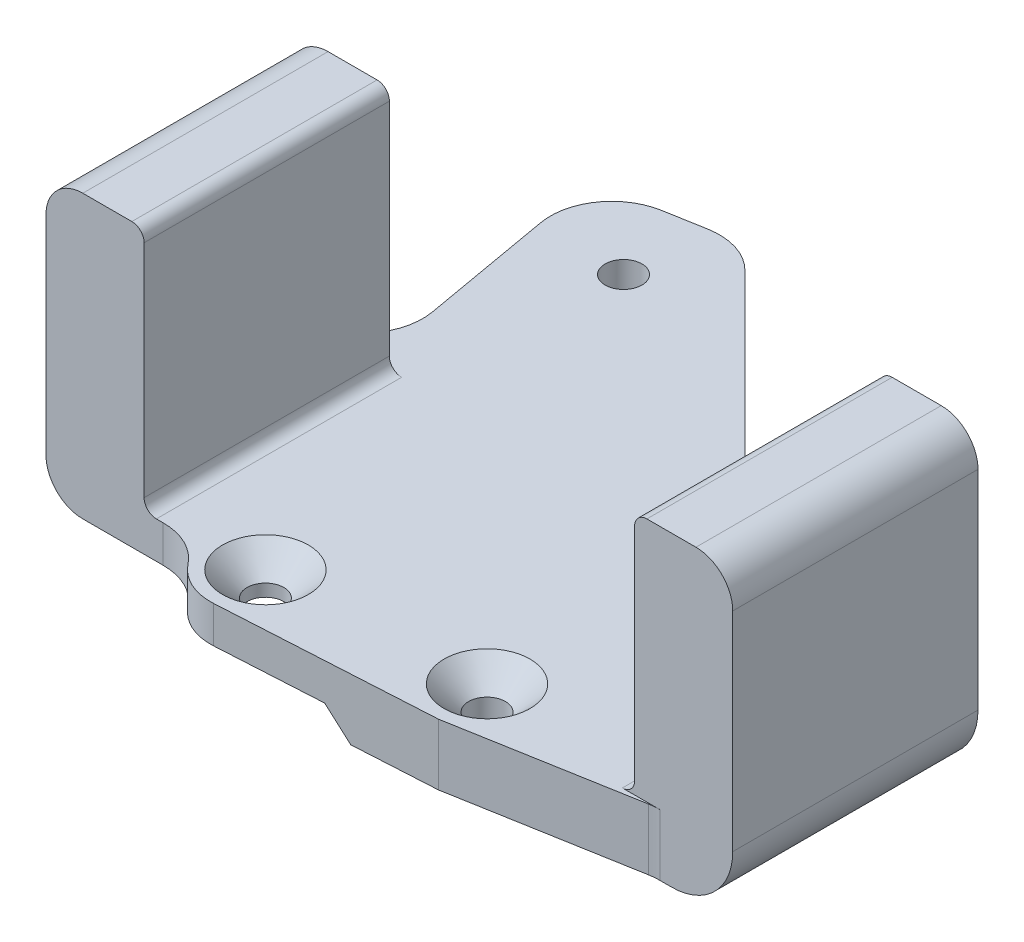
SolidWorks part; units mm, degrees
material "ABS"
ref_plane "Front" through (0, 0, 0) normal (0, 0, 1) x (1, 0, 0)
ref_plane "Top" through (0, 0, 0) normal (0, 1, 0) x (1, 0, 0)
ref_plane "Right" through (0, 0, 0) normal (1, 0, 0) x (0, 0, -1)
sketch "Esquisse1" plane through (0, 0, 0) normal (0, 0, 1) x (1, 0, 0)
  line L0 (20, 25) -> (28, 25)
  line L1 (-28, 25) -> (-20, 25)
  line L2 (-28, 25) -> (-28, 0)
  line L3 (-28, 0) -> (28, 0)
  line L4 (28, 25) -> (28, 0)
  line L6 (-20, 25) -> (-20, 5)
  line L7 (-20, 5) -> (20, 5)
  line L8 (20, 25) -> (20, 5)
  line L9 (0, -50) -> (0, 50) construction
  circle A0 centre (-24, 20) radius 0.85
  circle A1 centre (-24, 10) radius 0.85
  circle A2 centre (24, 10) radius 0.85
  circle A3 centre (24, 20) radius 0.85
  dimension "D1" = 10
  dimension "D2" = 48
  dimension "D6" = 5
  dimension "D7" = 1.7
  dimension "D9" = 4
  dimension "D3" = 40
  dimension "D4" = 5
  dimension "D5" = 5
  dimension "D8" = 56
  dimension "D10" = 8
  dimension "D11" = 25
extrude "Boss.-Extru.1" add sketch "Esquisse1" along normal blind 20
sketch "Esquisse2" plane through (0, 5, 0) normal (0, 1, 0) x (1, 0, 0)
  line L4 (28, -20) -> (28, 0) construction
  line L5 (-25.1177, 21.5152) -> (28, 30.8813)
  line L22 (-25.1177, 21.5152) -> (-16.6089, -26.7404)
  line L23 (-16.6089, -26.7404) -> (28, -18.8746)
  line L24 (28, 30.8813) -> (28, -18.8746)
  line L26 (20, 0) -> (-20, 0) construction
  dimension "D1" = 49
  dimension "D2" = 21
  dimension "D3" = 25.55
  dimension "D4" = 10
extrude "Boss.-Extru.2" add sketch "Esquisse2" against normal up to surface (5 mm away) up to face at (0, 0, 10)
sketch "Esquisse3" plane through (0, 5, 0) normal (0, 1, 0) x (1, 0, 0)
  line L0 (6.1284, -18.1635) -> (-0.4702, 19.2592) construction
  line L1 (-0.4702, 19.2592) -> (-17.212, 16.3072) construction
  line L2 (0, -50) -> (0, 50) construction
  line L3 (-17.212, 16.3072) -> (-10.9606, -19.1459) construction
  circle A0 centre (-17.212, 16.3072) radius 1.5
  circle A1 centre (6.1284, -18.1635) radius 1.5
  circle A2 centre (6.1284, -18.1635) radius 1.5 construction
  circle A3 centre (-10.9606, -19.1459) radius 1.5
  dimension "D1" = 3
  dimension "D2" = 17
  dimension "D3" = 38
  dimension "D4" = 10
  dimension "D5" = 36
extrude "Enlèv. mat.-Extru.1" cut sketch "Esquisse3" against normal through all
fillet "Congé1" radius 1 4 edges at (20, 25, 10) (-20, 25, 10) (20, 5, 10) (-20, 5, 10)
fillet "Congé2" radius 3 2 edges at (28, 25, 10) (-28, 25, 10) tangent propagation no
chamfer "Chanfrein2" distance 2 angle 45 2 edges at (6.1284, 5, 19.6635) (-10.9606, 5, 20.6459)
sketch "Esquisse4" plane through (0, 0, 0) normal (0, -1, 0) x (1, 0, 0)
  line L0 (21.6175, 20) -> (-16.6089, 26.7404) construction
  line L1 (-48.2397, 32.3177) -> (0.0159, 23.809)
  line L2 (-48.2397, 32.3177) -> (-56.7485, -15.9379)
  line L3 (-56.7485, -15.9379) -> (-8.4929, -24.4466)
  line L4 (0.0159, 23.809) -> (-8.4929, -24.4466)
  line L5 (-25.1177, -21.5152) -> (28, -30.8813) construction
  circle A0 centre (-17.212, -16.3072) radius 1.5 construction
  dimension "D1" = 10
extrude "Enlèv. mat.-Extru.2" cut sketch "Esquisse4" against normal blind 2
chamfer "Chanfrein3" distance 2 angle 45 1 edges at (-4.2385, 2, -0.3188)
sketch "Esquisse5" plane through (0, 5, 0) normal (0, 1, 0) x (1, 0, 0)
  line L1 (-28, -20) -> (-15.377, -20)
  line L2 (-28, -20) -> (-28, -26.7404)
  line L3 (-28, -26.7404) -> (6.6498, -26.7404)
  line L4 (6.6498, -22.6392) -> (6.6498, -26.7404)
  line L5 (25, 0) -> (21, 0) construction
  line L6 (28, 30.8813) -> (-21.8866, 30.8813)
  line L7 (28, 30.8813) -> (28, 0)
  line L8 (28, 0) -> (8.9947, 0)
  line L9 (-21.8866, 30.8813) -> (8.9947, 0)
  line L10 (-10.7025, -23.6367) -> (6.6498, -22.6392)
  line L11 (-16.6089, -26.7404) -> (21.6175, -20) construction
  arc A0 (-15.377, -20) -> (-10.7025, -23.6367) centre (-10.9606, -19.1459) ccw
  circle A2 centre (-17.212, 16.3072) radius 1.5 construction
  circle A3 centre (-10.9606, -19.1459) radius 1.5 construction
  circle A4 centre (6.1284, -18.1635) radius 4.4982 construction
  circle A5 centre (6.1284, -18.1635) radius 1.5 construction
  dimension "D1" = 7
  dimension "D2" = 45
extrude "Enlèv. mat.-Extru.3" cut sketch "Esquisse5" against normal through all
fillet "Congé3" radius 5 7 edges at (-15.377, 3.5, 20) (-21.324, 3.5, 0) (-25.1177, 3.5, -21.5152) (-14.4088, 3.5, -23.4035) (8.9947, 2.5, 0) (28, 0, 10) (21.6175, 2.5, 20)
fillet "Congé4" radius 3 1 edges at (-28, 2, 10)
sketch "Esquisse6" plane through (0, 0, 20) normal (0, 0, 1) x (1, 0, 0)
  line L6 (-28, 22) -> (-28, 5)
  line L7 (-25, 2) -> (-18.4403, 2)
  line L8 (-18.4403, 2) -> (-18.4403, 5)
  line L9 (-18.4403, 5) -> (-19, 5)
  line L10 (-20, 6) -> (-20, 24)
  line L11 (-21, 25) -> (-25, 25)
  line L12 (-28, 22) -> (-28, 5)
  line L13 (-25, 2) -> (-18.4403, 2)
  line L14 (-18.4403, 2) -> (-18.4403, 5)
  line L15 (-18.4403, 5) -> (-19, 5)
  line L16 (-20, 6) -> (-20, 24)
  line L17 (-21, 25) -> (-25, 25)
  line L18 (19, 5) -> (22.055, 5)
  line L19 (22.055, 5) -> (22.055, 0)
  line L20 (22.055, 0) -> (23, 0)
  line L21 (28, 5) -> (28, 22)
  line L22 (25, 25) -> (21, 25)
  line L23 (20, 24) -> (20, 6)
  line L24 (19, 5) -> (22.055, 5)
  line L25 (22.055, 5) -> (22.055, 0)
  line L26 (22.055, 0) -> (23, 0)
  line L27 (28, 5) -> (28, 22)
  line L28 (25, 25) -> (21, 25)
  line L29 (20, 24) -> (20, 6)
  arc A4 (-28, 5) -> (-25, 2) centre (-25, 5) ccw
  arc A5 (-20, 6) -> (-19, 5) centre (-19, 6) ccw
  arc A6 (-20, 24) -> (-21, 25) centre (-21, 24) ccw
  arc A7 (-25, 25) -> (-28, 22) centre (-25, 22) ccw
  arc A8 (-28, 5) -> (-25, 2) centre (-25, 5) ccw
  arc A9 (-20, 6) -> (-19, 5) centre (-19, 6) ccw
  arc A10 (-20, 24) -> (-21, 25) centre (-21, 24) ccw
  arc A11 (-25, 25) -> (-28, 22) centre (-25, 22) ccw
  arc A12 (23, 0) -> (28, 5) centre (23, 5) ccw
  arc A13 (28, 22) -> (25, 25) centre (25, 22) ccw
  arc A14 (21, 25) -> (20, 24) centre (21, 24) ccw
  arc A15 (19, 5) -> (20, 6) centre (19, 6) ccw
  arc A16 (23, 0) -> (28, 5) centre (23, 5) ccw
  arc A17 (28, 22) -> (25, 25) centre (25, 22) ccw
  arc A18 (21, 25) -> (20, 24) centre (21, 24) ccw
  arc A19 (19, 5) -> (20, 6) centre (19, 6) ccw
  dimension "D1" = 0
  dimension "D2" = 0
extrude "Boss.-Extru.3" add sketch "Esquisse6" against normal blind 0.2
